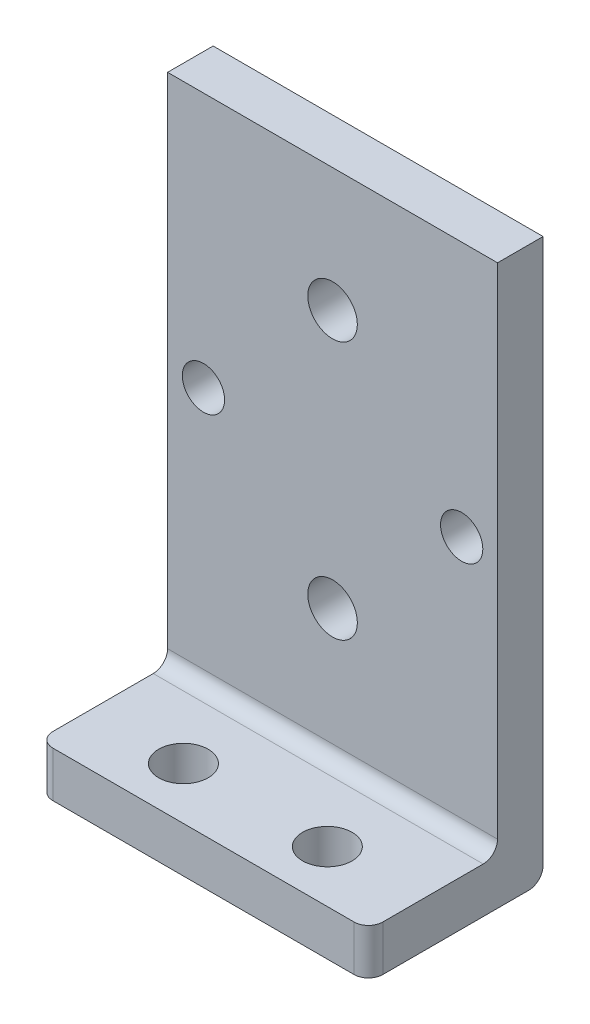
SolidWorks part; units mm, degrees
note: The reader was unsure of these and kept them because the rebuilt part matched: shared geometry of "Sketch1<3>".
ref_plane "Front Plane" through (0, 0, 0) normal (0, 0, 1) x (1, 0, 0)
ref_plane "Top Plane" through (0, 0, 0) normal (0, 1, 0) x (1, 0, 0)
ref_plane "Right Plane" through (0, 0, 0) normal (1, 0, 0) x (0, 0, -1)
sketch "Sketch1" plane through (0, 0, 0) normal (0, 0, 1) x (1, 0, 0)
  line L0 (0, -20) -> (23, -20)
  line L1 (0, 0) -> (23, 0)
  line L2 (0, 0) -> (0, -23.175)
  line L3 (0, -23.175) -> (23, -23.175)
  line L4 (23, 0) -> (23, -23.175)
  line L5 (0, 0) -> (0, 2)
  line L6 (0, 2) -> (23, 2)
  line L7 (23, 2) -> (23, 0)
  line L8 (11.5, 7.1821) -> (11.5, -10.8179) construction
  line L10 (0, 2) -> (23, 2)
  line L11 (0, 2) -> (0, 15.7952)
  line L12 (0, 15.7952) -> (23, 15.7952)
  line L13 (23, 2) -> (23, 15.7952)
  circle A0 centre (2.5, -2) radius 1.4732
  circle A1 centre (20.5, -2) radius 1.4732
  circle A2 centre (11.5, 7.1821) radius 1.7272
  circle A3 centre (11.5, -10.8179) radius 1.7272
  point P17 (11.5, -1.8179)
  point P18 (11.5, 2)
  dimension "D2" = 2.9464
  dimension "D10" = 3.4544
  dimension "D1" = 18
  dimension "D4" = 3.175
  dimension "D5" = 23
  dimension "D6" = 2.5
  dimension "D7" = 2
  dimension "D3" = 20
  dimension "D8" = 2
  dimension "D9" = 18
extrude "Boss-Extrude1" add sketch "Sketch1" along normal blind 3.175
extrude "Boss-Extrude2" add sketch "Sketch1<3>" along normal blind 9 from surface at 3.175 contours L4 L0 L2 L3 starting at face at (11.5, -3.6899, 3.175)
sketch "Sketch1<3>" plane through (0, 0, 0) normal (0, 0, 1) x (1, 0, 0) same geometry as "Sketch1"
sketch "Mount Hole Location" plane through (0, -20, 0) normal (0, 1, 0) x (1, 0, 0)
  line L0 (0, -12.175) -> (23, -12.175) construction
  line L1 (8.579, -8.5555) -> (14.421, -8.5555) construction
  line L3 (0, -4.809) -> (23, -4.809) construction
  line L4 (0, -12.175) -> (0, -3.175) construction
  line L5 (23, -12.175) -> (23, -3.175) construction
  line L6 (23, -12.175) -> (0, -12.175) construction
  line L7 (6.4835, -6.46) -> (6.4835, -4.809) construction
  circle A0 centre (16.5165, -8.5555) radius 3.4925 construction
  circle A1 centre (16.5165, -8.5555) radius 2.0955
  circle A2 centre (6.4835, -8.5555) radius 2.0955
  circle A3 centre (6.4835, -8.5555) radius 3.4925 construction
  point P0 (11.5, -8.5555)
  point P4 (11.5, -12.175)
  point P15 (11.5, -8.5555)
  dimension "D2" = 6.985
  dimension "D3" = 4.191
  dimension "D1" = 1.651
  dimension "D4" = 5.842
  dimension "D5" = 7.366
hole_wizard "#8-32 Tapped Hole1" positions "3DSketch1" profile "Sketch3" tap size "#8-32" standard "ANSI Inch" end condition through all
sketch3d "3DSketch1"
  point P5 (6.4835, -20, 8.5555)
  point P8 (16.5165, -20, 8.5555)
sketch "Sketch3" plane through (6.4835, -20, 8.5555) normal (1, 0, 0) x (0, 0, 1)
  line L0 (0, 0) -> (0, 3.175)
  line L1 (0, 3.175) -> (1.7272, 3.175)
  line L2 (1.7272, 3.175) -> (1.7272, 0)
  line L5 (1.7272, 0) -> (0, 0)
  line L11 (0, -6.35) -> (0, 107.95) construction
  dimension "Thru Tap Drill Dia." = 3.4544
  dimension "Thru Tap Drill Depth" = 3.175
cosmetic thread "Hole Thread1"
cosmetic thread "Hole Thread2"
fillet "Fillet1" radius 1 4 edges at (0, -21.5875, 12.175) (23, -21.5875, 12.175) (11.5, -23.175, 0) (11.5, -20, 3.175)
equation "\"D6@Sketch1\"=(\"D5@Sketch1\"-\"D1@Sketch1\")/2"
